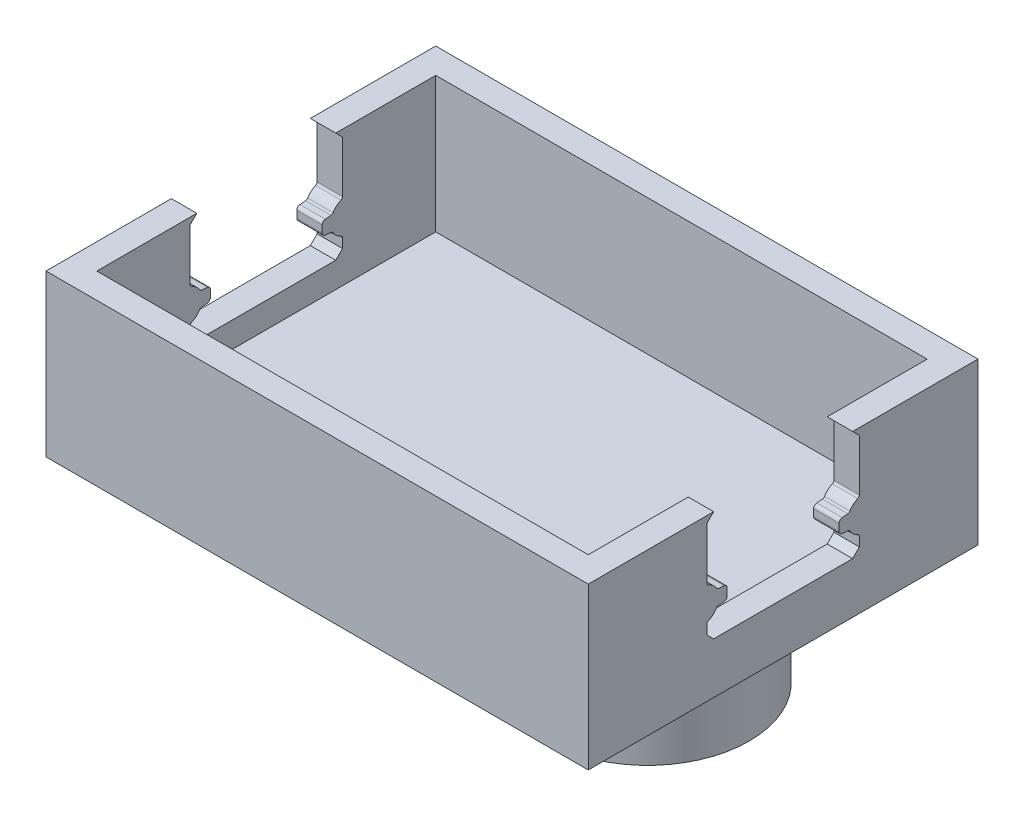
SolidWorks part; units mm, degrees
ref_plane "Front Plane" through (0, 0, 0) normal (0, 0, 1) x (1, 0, 0)
ref_plane "Top Plane" through (0, 0, 0) normal (0, 1, 0) x (1, 0, 0)
ref_plane "Right Plane" through (0, 0, 0) normal (1, 0, 0) x (0, 0, -1)
sketch "Sketch4" plane through (0, 0, 0) normal (0, 1, 0) x (1, 0, 0)
  line L1 (-16, -11.5) -> (16, -11.5)
  line L2 (-16, -11.5) -> (-16, 11.5)
  line L3 (-16, 11.5) -> (16, 11.5)
  line L4 (16, -11.5) -> (16, 11.5)
  line L5 (-16, -11.5) -> (16, 11.5) construction
  line L6 (-16, 11.5) -> (16, -11.5) construction
  point P0 (0, 0)
  dimension "D1" = 32
  dimension "D2" = 23
extrude "Boss-Extrude3" add sketch "Sketch4" along normal blind 9.5
sketch "Sketch5" plane through (0, 9.5, 0) normal (0, 1, 0) x (1, 0, 0)
  line L1 (-14.5, -10) -> (14.5, -10)
  line L2 (-14.5, -10) -> (-14.5, 10)
  line L3 (-14.5, 10) -> (14.5, 10)
  line L4 (14.5, -10) -> (14.5, 10)
  line L5 (-14.5, -10) -> (14.5, 10) construction
  line L6 (-14.5, 10) -> (14.5, -10) construction
  point P0 (0, 0)
  dimension "D1" = 29
  dimension "D2" = 20
extrude "Cut-Extrude2" cut sketch "Sketch5" against normal blind 8
sketch "Sketch8" plane through (-16, 0, 0) normal (-1, 0, 0) x (0, 0, 1)
  line L2 (-11.5, 9.5) -> (11.5, 9.5) construction
  line L4 (11.5, 9.5) -> (11.5, 0) construction
  line L8 (-2.2, 9.5) -> (-1.4, 9.5)
  spline S0 degree 3 poles (-2.2, 9.5) (-2.1353, 9.2413) (-1.5778, 9.0675) (-1.4, 9.5) knots 0 0 0 0 1 1 1 1
  line B0 (4.5, 6.0583) -> (4.5, 9.1)
  line B1 (4.5, 9.1) -> (4.1, 9.5)
  line B2 (4.1, 9.5) -> (-1.4, 9.5)
  line B3 (-2.2, 9.5) -> (-4.1, 9.5)
  line B4 (-4.1, 9.5) -> (-4.5, 9.1)
  line B5 (-4.5, 9.1) -> (-4.5, 6.0583)
  line B6 (-3.8235, 5.4365) -> (-3.4826, 5.4066)
  line B7 (-3.3, 5.2074) -> (-3.3, 4.7926)
  line B8 (-3.4826, 4.5934) -> (-3.8235, 4.5635)
  line B9 (-4.5, 3.9417) -> (-4.5, 3.4)
  line B10 (-4.5, 3.4) -> (-4.1, 3)
  line B11 (-4.1, 3) -> (4.1, 3)
  line B12 (4.1, 3) -> (4.5, 3.4)
  line B13 (4.5, 3.4) -> (4.5, 3.9417)
  line B14 (3.8235, 4.5635) -> (3.4826, 4.5934)
  line B15 (3.3, 4.7926) -> (3.3, 5.2074)
  line B16 (3.4826, 5.4066) -> (3.8235, 5.4365)
  arc B17 (-2.2, 9.5) -> (-1.4, 9.5) centre (-1.8, 9.8) ccw
  arc B18 (-4.5, 6.0583) -> (-4.4087, 5.9203) centre (-4.35, 6.0583) ccw
  arc B19 (-3.9395, 5.5095) -> (-4.4087, 5.9203) centre (-4.8, 5) ccw
  arc B20 (-3.9395, 5.5095) -> (-3.8235, 5.4365) centre (-3.8104, 5.5859) ccw
  arc B21 (-3.3, 5.2074) -> (-3.4826, 5.4066) centre (-3.5, 5.2074) ccw
  arc B22 (-3.4826, 4.5934) -> (-3.3, 4.7926) centre (-3.5, 4.7926) ccw
  arc B23 (-3.8235, 4.5635) -> (-3.9395, 4.4905) centre (-3.8104, 4.4141) ccw
  arc B24 (-4.4087, 4.0797) -> (-3.9395, 4.4905) centre (-4.8, 5) ccw
  arc B25 (-4.4087, 4.0797) -> (-4.5, 3.9417) centre (-4.35, 3.9417) ccw
  arc B26 (4.5, 3.9417) -> (4.4087, 4.0797) centre (4.35, 3.9417) ccw
  arc B27 (3.9395, 4.4905) -> (4.4087, 4.0797) centre (4.8, 5) ccw
  arc B28 (3.9395, 4.4905) -> (3.8235, 4.5635) centre (3.8104, 4.4141) ccw
  arc B29 (3.3, 4.7926) -> (3.4826, 4.5934) centre (3.5, 4.7926) ccw
  arc B30 (3.4826, 5.4066) -> (3.3, 5.2074) centre (3.5, 5.2074) ccw
  arc B31 (3.8235, 5.4365) -> (3.9395, 5.5095) centre (3.8104, 5.5859) ccw
  arc B32 (4.4087, 5.9203) -> (3.9395, 5.5095) centre (4.8, 5) ccw
  arc B33 (4.4087, 5.9203) -> (4.5, 6.0583) centre (4.35, 6.0583) ccw
  line M194 (11.5, 9.5) -> (-11.5, 9.5)
  dimension "D1" = 7
sketch_block_instance "9mm Block-2"
sketch_block "9mm Block"
extrude "Cut-Extrude4" cut sketch "Sketch8" against normal up to surface (32 mm away) contours B32 B33 B0 B1 S0 B4 B5 B18 B19 B20 B6 B21 B7 B22 B8 B23 B24 B25 B9 B10 B11 B12 B13 B26 B27 B28 B14 B29 B15 B30 B16 B31 M194 | B17 M194 | B17 S0 region at (-16, 9.2916, -1.8) region at (-16, 6.3052, 0.005) region at (-16, 9.4184, -1.8) up to face at (16, 4.75, 0)
sketch "Sketch9" plane through (0, 0, 0) normal (0, -1, 0) x (-1, 0, 0)
  line L0 (16, -11.5) -> (-16, -11.5) construction
  line L1 (0, -11.5) -> (0, 11.5) construction
  line L2 (-16, 11.5) -> (16, 11.5) construction
  line L3 (0, -11.5) -> (16, 11.5) construction
  line L4 (16, -11.5) -> (0, 11.5) construction
  circle A0 centre (8, 0) radius 4.8125
  circle A1 centre (8, 0) radius 6
  circle A2 centre (-8, 0) radius 4.8125
  circle A3 centre (-8, 0) radius 6
  dimension "D1" = 9.625
  dimension "D2" = 12
extrude "Boss-Extrude5" add sketch "Sketch9" along normal blind 3.275 contours A1 | A3 | A2 | A0
sketch "Sketch10" plane through (0, -3.275, 0) normal (0, -1, 0) x (-1, 0, 0)
  line L0 (0, -11.5) -> (0, 11.5) construction
  line L1 (16, -11.5) -> (-16, -11.5) construction
  line L2 (-16, 11.5) -> (16, 11.5) construction
  circle A0 centre (8, 0) radius 6
  circle A1 centre (8, 0) radius 3.6
  circle A2 centre (-8, 0) radius 3.6
  circle A3 centre (-8, 0) radius 6
  dimension "D1" = 12
  dimension "D2" = 7.2
extrude "Boss-Extrude6" add sketch "Sketch10" along normal blind 2
